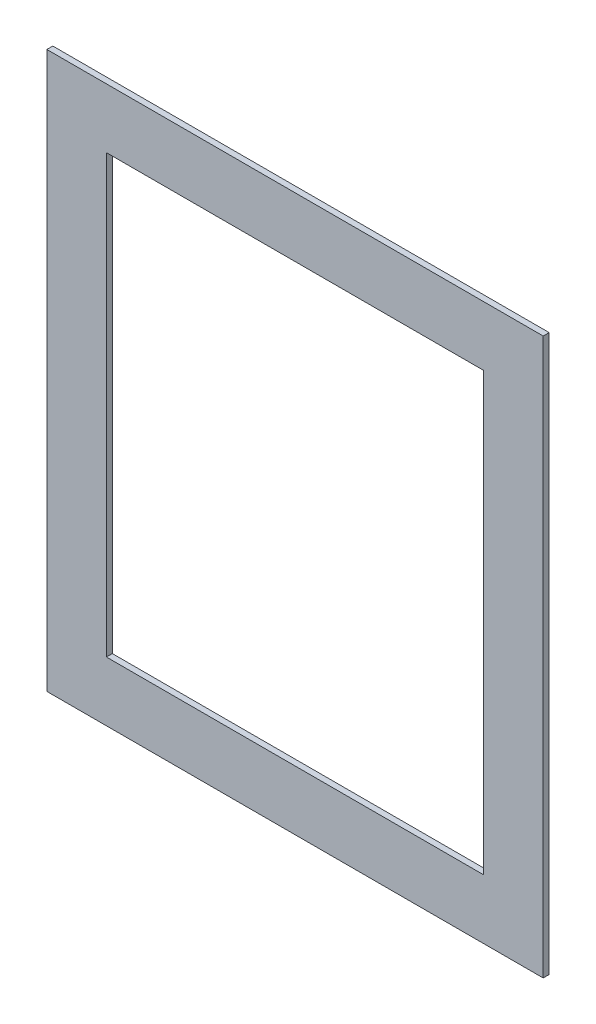
SolidWorks part; units mm, degrees
material "Клен"
ref_plane "Спереди" through (0, 0, 0) normal (0, 0, 1) x (1, 0, 0)
ref_plane "Сверху" through (0, 0, 0) normal (0, 1, 0) x (1, 0, 0)
ref_plane "Справа" through (0, 0, 0) normal (1, 0, 0) x (0, 0, -1)
sketch "Эскиз1" plane through (0, 0, 0) normal (0, 0, 1) x (1, 0, 0)
  line L0 (2.3279, 480.4642) -> (2.3279, 40.4642)
  line L1 (-57.6721, 540.4642) -> (442.3279, 540.4642)
  line L2 (-57.6721, 540.4642) -> (-57.6721, -19.5358)
  line L3 (-57.6721, -19.5358) -> (442.3279, -19.5358)
  line L4 (442.3279, 540.4642) -> (442.3279, -19.5358)
  line L5 (2.3279, 40.4642) -> (382.3279, 40.4642)
  line L6 (382.3279, 480.4642) -> (382.3279, 40.4642)
  line L7 (2.3279, 480.4642) -> (382.3279, 480.4642)
  dimension "D1" = 560
  dimension "D2" = 500
  dimension "D3" = 60
extrude "Бобышка-Вытянуть1" add sketch "Эскиз1" along normal blind 6
equation "\"D1@Эскиз1\" = 500 + \"bottom_line\""
equation "\"sheet_thickness\"= 6"
equation "\"D1@Бобышка-Вытянуть1\"= \"sheet_thickness\""
equation "\"bottom_line\"= 60"
equation "\"width_space\"= 500"
equation "\"D2@Эскиз1\"= \"width_space\""
equation "\"D3@Эскиз1\"= \"bottom_line\""
